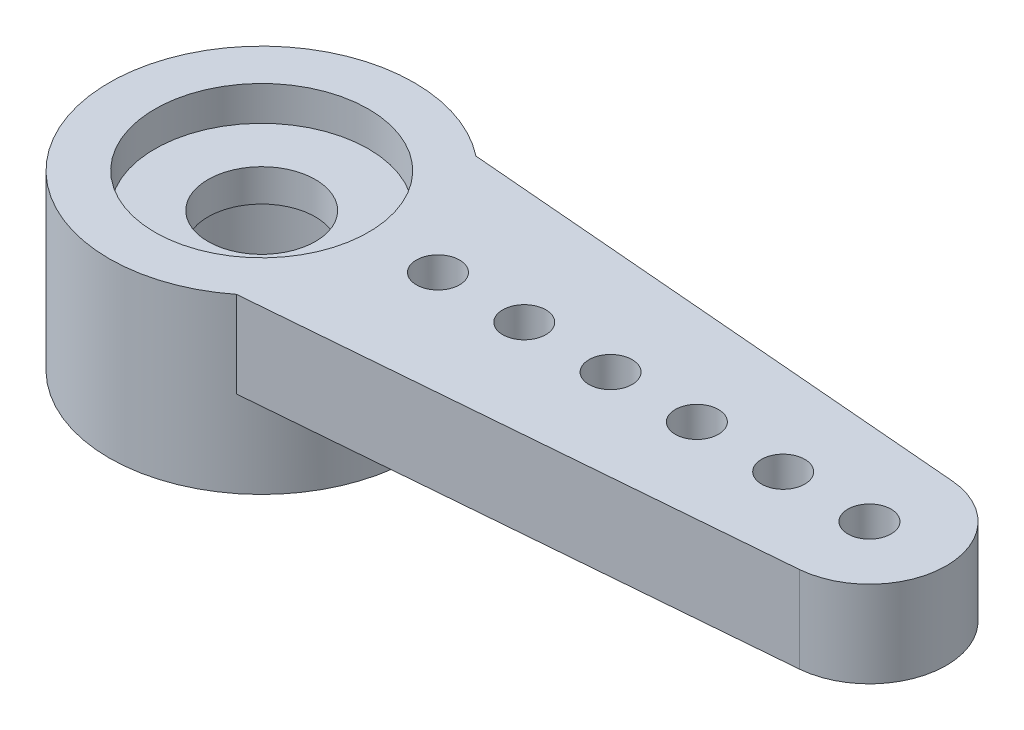
SolidWorks part; units mm, degrees
material "PMMA"
ref_plane "Front Plane" through (0, 0, 0) normal (0, 0, 1) x (1, 0, 0)
ref_plane "Top Plane" through (0, 0, 0) normal (0, 1, 0) x (1, 0, 0)
ref_plane "Right Plane" through (0, 0, 0) normal (1, 0, 0) x (0, 0, -1)
ref_axis "X-Axis" through (-88.99, 0, 0) along (1, 0, 0)
ref_axis "Y-Axis" through (0, 0, -88.99) along (0, 0, 1)
ref_axis "Z-Axis" through (0, 55, 0) along (0, -1, 0)
sketch "Sketch2" plane through (0, 0, 0) normal (0, 0, 1) x (1, 0, 0)
  line L0 (0, 0) -> (0, -2) construction
  line L1 (2.475, 2) -> (2.475, 1.2)
  line L2 (2.475, 1.2) -> (1.245, 1.2)
  line L3 (1.245, 1.2) -> (1.245, 0.45)
  line L4 (1.245, 0.45) -> (2.375, 0.45)
  line L5 (2.375, 0.45) -> (2.375, -2)
  line L6 (2.375, -2) -> (3.535, -2)
  line L7 (3.535, -2) -> (3.535, 2)
  line L8 (3.535, 2) -> (2.475, 2)
  dimension "D1" = 4.75
  dimension "D2" = 2.49
  dimension "D3" = 4.95
  dimension "D4" = 0.8
  dimension "D5" = 7.07
  dimension "D6" = 2
  dimension "D7" = 2.45
  dimension "D8" = 4
revolve "Revolve1" add sketch "Sketch2" angle 360 about axis through (0, 55, 0) along (0, -1, 0)
sketch "Sketch3" plane through (0, 0, 0) normal (0, 1, 0) x (1, 0, 0)
  line L0 (2.1899, -2.775) -> (14.2325, -1.7739)
  line L1 (0, 0) -> (20.2296, 0) construction
  line L2 (-3.535, 0) -> (15.865, 0) construction
  line L3 (2.1899, -2.775) -> (2.1899, 0)
  line L4 (2.1899, 0) -> (15.865, 0)
  circle A0 centre (0, 0) radius 3.535 construction
  circle A1 centre (14.085, 0) radius 1.78
  circle A2 centre (0, 0) radius 3.535
  circle A3 centre (14.085, 0) radius 0.5
  circle A4 centre (12.085, 0) radius 0.5
  circle A5 centre (10.085, 0) radius 0.5
  circle A6 centre (8.085, 0) radius 0.5
  circle A7 centre (6.085, 0) radius 0.5
  circle A8 centre (4.085, 0) radius 0.5
  dimension "D2" = 3.56
  dimension "D5" = 6
  dimension "D1" = 2.775
  dimension "D4" = 1
  dimension "D3" = 19.4
extrude "Boss-Extrude1" add sketch "Sketch3" along normal up to surface (2 mm away) contours A8 L4 A2 L0 A1 A4 A5 A6 A7 | A4 A1 L4 A3 region at (7.6377, 0, 1.3069) region at (14.1152, 0, 0.8137) up to face at (0, 2, 2.475)
mirror "Mirror1" about plane through (0, 15.9538, 0) normal (0, 0, -1) of "Boss-Extrude1"
sketch "草图1" plane through (0, 0, 0) normal (0, 1, 0) x (1, 0, 0)
  line L0 (0, 0) -> (35.5707, 0) construction
  line L1 (14.2325, 1.7739) -> (35.5707, 0) construction
  line L2 (14.2325, 1.7739) -> (2.1899, 2.775)
  line L3 (2.1899, -2.775) -> (14.2325, -1.7739)
  line L4 (14.2325, 1.7739) -> (2.1899, 2.775)
  line L5 (2.1899, -2.775) -> (14.2325, -1.7739)
  line L6 (35.5707, 0) -> (14.2325, -1.7739) construction
  line L7 (0, 0) -> (2.1899, 2.775) construction
  line L8 (0, 0) -> (2.1899, -2.775) construction
  arc A2 (2.1899, 2.775) -> (2.1899, -2.775) centre (0, 0) ccw
  arc A3 (14.2325, -1.7739) -> (14.2325, 1.7739) centre (14.085, 0) ccw
  arc A4 (2.1899, 2.775) -> (2.1899, -2.775) centre (0, 0) ccw
  arc A5 (14.2325, -1.7739) -> (14.2325, 1.7739) centre (14.085, 0) ccw
  dimension "D1" = 0
